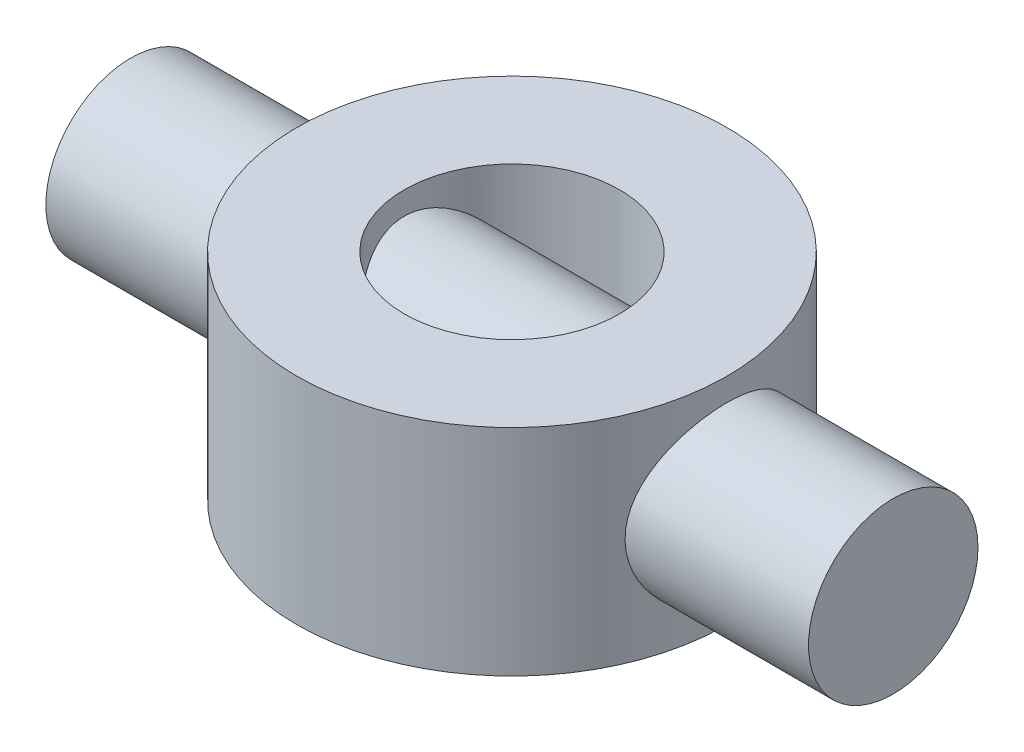
SolidWorks part; units mm, degrees
ref_plane "Front Plane" through (0, 0, 0) normal (0, 0, 1) x (1, 0, 0)
ref_plane "Top Plane" through (0, 0, 0) normal (0, 1, 0) x (1, 0, 0)
ref_plane "Right Plane" through (0, 0, 0) normal (1, 0, 0) x (0, 0, -1)
sketch "Sketch1" plane through (0, 0, 0) normal (0, 1, 0) x (1, 0, 0)
  circle A0 centre (0, 0) radius 12.7
  circle A1 centre (0, 0) radius 25.4
  dimension "D1" = 50.8
sketch "Sketch2" plane through (0, 0, 0) normal (1, 0, 0) x (0, 0, -1)
  line L0 (25.4, 0) -> (-25.4, 0) construction
  circle A0 centre (0, 0) radius 10
extrude "Boss-Extrude1" add sketch "Sketch2" along normal blind 45 and the other way blind 45
extrude "Boss-Extrude2" add sketch "Sketch1" along normal blind 12.7 and the other way blind 12.7
equation "\"toothBaseWidth\"=0.01"
equation "\"toothEndWidth\"=0.009"
equation "\"toothLength\"= 0.005715"
equation "\"holeWidth\" = 0.009"
equation "\"motorHolderToothSeparation\" = 0.01"
equation "\"magnetHolderToothSeparation\" = 0.02"
equation "\"magnetWidth\" = 0.0127"
equation "\"quarterInch\" = 0.005715"
equation "\"coilThickness\" = 0.0254"
equation "\"coilOuterDiameter\" = 0.0508"
equation "\"D1@Sketch1\"= \"coilOuterDiameter\""
equation "\"D1@Boss-Extrude2\"= \"coilThickness\"/2"
equation "\"D2@Boss-Extrude2\"= \"coilThickness\"/2"
